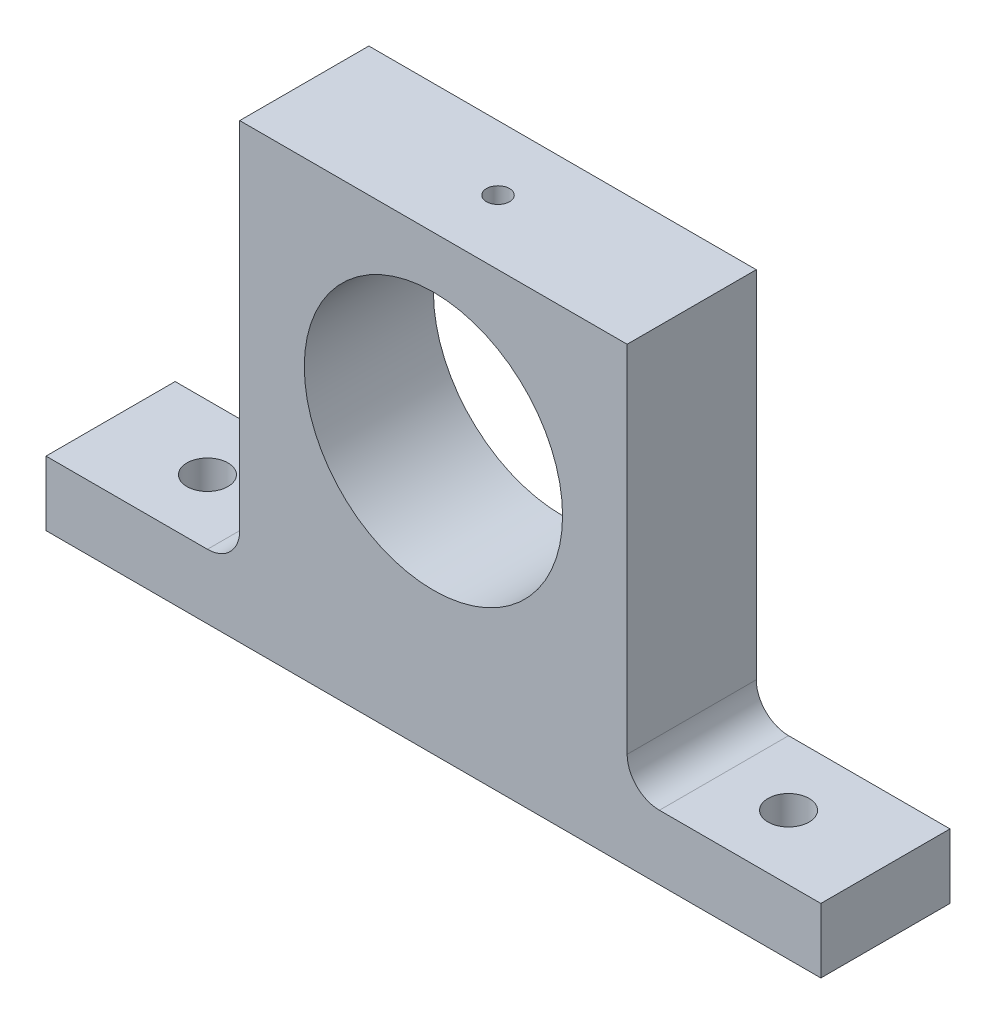
SolidWorks part; units mm, degrees
material "1060 Alloy"
ref_plane "Front Plane" through (0, 0, 0) normal (0, 0, 1) x (1, 0, 0)
ref_plane "Top Plane" through (0, 0, 0) normal (0, 1, 0) x (1, 0, 0)
ref_plane "Right Plane" through (0, 0, 0) normal (1, 0, 0) x (0, 0, -1)
sketch "Sketch1" plane through (0, 0, 0) normal (0, 0, 1) x (1, 0, 0)
  line L0 (38.1, 0) -> (-38.1, 0)
  line L1 (-38.1, 0) -> (-38.1, 6.35)
  line L2 (-38.1, 6.35) -> (-19.05, 6.35)
  line L3 (-19.05, 6.35) -> (-19.05, 44.45)
  line L4 (-19.05, 44.45) -> (19.05, 44.45)
  line L5 (0, 44.45) -> (0, 0) construction
  line L6 (19.05, 6.35) -> (19.05, 44.45)
  line L7 (38.1, 6.35) -> (19.05, 6.35)
  line L8 (38.1, 0) -> (38.1, 6.35)
  line L9 (-7.5, 26.67) -> (7.5, 26.67) construction
  line L10 (-7.5, 18.448) -> (-7.5, 34.892) construction
  line L11 (7.5, 34.892) -> (7.5, 18.448) construction
  circle A0 centre (0, 26.67) radius 12.7
  point P13 (0, 13.97)
  dimension "D5" = 25.4
  dimension "D1" = 6.35
  dimension "D2" = 19.05
  dimension "D3" = 38.1
  dimension "D4" = 19.05
extrude "Boss-Extrude1" add sketch "Sketch1" along normal blind 12.7
hole_wizard "#10-32 Tapped Hole1" positions "3DSketch1" profile "Sketch4" tap size "#10-32" standard "Ansi Inch" end condition through all
sketch3d "3DSketch1"
  line L0 (-38.1, 6.35, 6.35) -> (-19.05, 6.35, 6.35) construction
  line L1 (-38.1, 6.35, 12.7) -> (-38.1, 6.35, 0) construction
  line L2 (-19.05, 6.35, 12.7) -> (-19.05, 6.35, 0) construction
  line L8 (19.05, 6.35, 6.35) -> (38.1, 6.35, 6.35) construction
  line L9 (19.05, 6.35, 12.7) -> (19.05, 6.35, 0) construction
  line L10 (38.1, 6.35, 12.7) -> (38.1, 6.35, 0) construction
  point P0 (-28.575, 6.35, 6.35)
  point P23 (28.575, 6.35, 6.35)
sketch "Sketch4" plane through (-28.575, 6.35, 6.35) normal (1, 0, 0) x (0, 0, 1)
  line L0 (0, 0) -> (0, 6.35)
  line L1 (0, 6.35) -> (2.0193, 6.35)
  line L2 (2.0193, 6.35) -> (2.0193, 0)
  line L5 (2.0193, 0) -> (0, 0)
  line L11 (0, -6.35) -> (0, 107.95) construction
  dimension "Thru Tap Drill Dia." = 4.0386
  dimension "Thru Tap Drill Depth" = 6.35
cosmetic thread "Hole Thread1" parameters "D2"=4.826
cosmetic thread "Hole Thread2" parameters "D2"=4.826
hole_wizard "#4-40 Tapped Hole1" positions "Sketch6" profile "Sketch5" tap size "#4-40" standard "Ansi Inch"
sketch "Sketch6" plane through (0, 44.45, 0) normal (0, 1, 0) x (-1, 0, 0)
  line L0 (19.05, 6.35) -> (-19.05, 6.35) construction
  line L1 (19.05, 12.7) -> (19.05, 0) construction
  line L2 (-19.05, 12.7) -> (-19.05, 0) construction
  point P0 (0, 6.35)
sketch "Sketch5" plane through (0, 44.45, 6.35) normal (1, 0, 0) x (0, 0, 1)
  line L0 (0, 0) -> (0, 18.4582)
  line L1 (0, 18.4582) -> (1.1303, 17.779)
  line L2 (1.1303, 17.779) -> (1.1303, 0)
  line L5 (1.1303, 0) -> (0, 0)
  line L10 (0, 18.4582) -> (-1.1303, 17.779) construction
  line L11 (0, -6.35) -> (0, 107.95) construction
  dimension "Tap Drill Dia." = 2.2606
  dimension "Tap Drill Depth" = 17.779
  dimension "Drill Angle" = 118
cosmetic thread "Hole Thread3" parameters "D1"=5.1304, "D2"=2.8448
fillet "Fillet1" radius 3.175 2 edges at (-19.05, 6.35, 6.35) (19.05, 6.35, 6.35)
